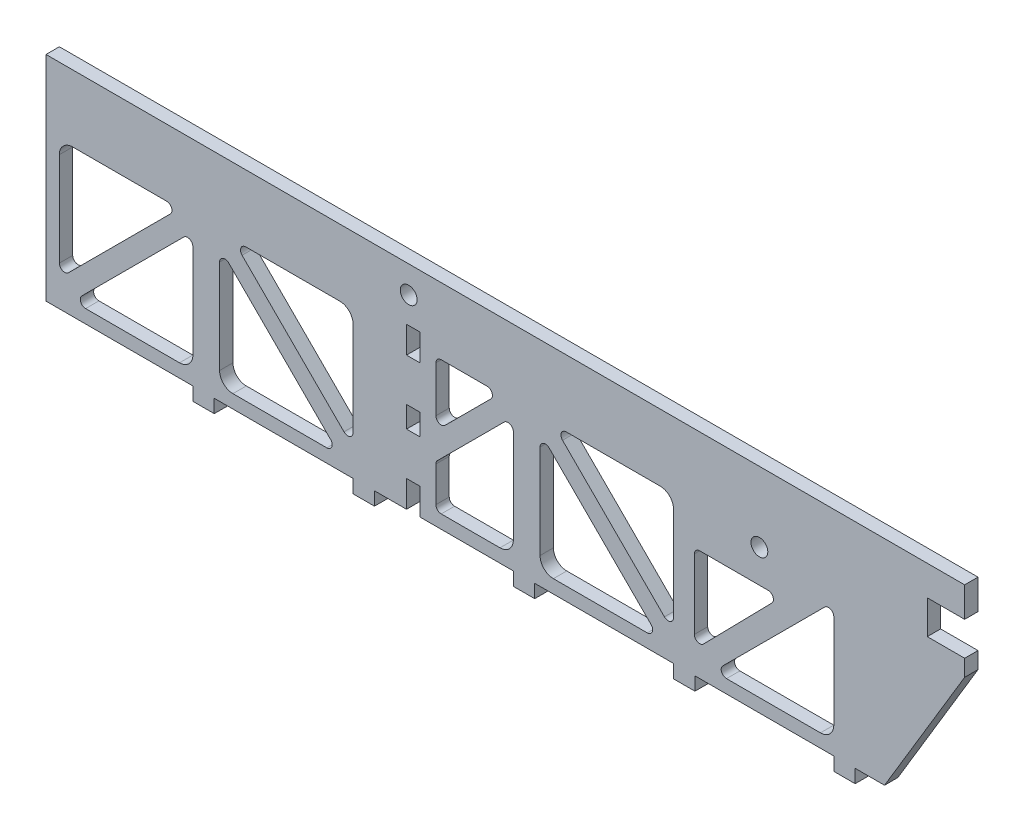
SolidWorks part; units mm, degrees
material "Pine"
ref_plane "Front Plane" through (0, 0, 0) normal (0, 0, 1) x (1, 0, 0)
ref_plane "Top Plane" through (0, 0, 0) normal (0, 1, 0) x (1, 0, 0)
ref_plane "Right Plane" through (0, 0, 0) normal (1, 0, 0) x (0, 0, -1)
sketch "Model" plane through (0, 0, 0) normal (0, 0, 1) x (1, 0, 0)
  line L0 (312.6855, 15.1239) -> (345.2281, 48.2988)
  line L1 (343.4149, 52.6175) -> (310.8722, 52.6175)
  line L2 (308.3322, 50.0775) -> (308.3322, 16.9026)
  line L8 (171.2321, 6.35) -> (215.9, 6.35)
  line L9 (217.9139, 59.1639) -> (169.4361, 10.6861)
  line L10 (222.25, 57.3679) -> (222.25, 12.7)
  line L11 (234.95, 57.3679) -> (234.95, 12.7)
  line L12 (239.2861, 59.1639) -> (287.7639, 10.6861)
  line L13 (241.3, 6.35) -> (285.9679, 6.35)
  line L14 (294.1139, 17.0361) -> (245.6361, 65.5139)
  line L15 (247.4321, 69.85) -> (292.1, 69.85)
  line L16 (298.45, 63.5) -> (298.45, 18.8321)
  line L17 (323.6321, 6.35) -> (368.3, 6.35)
  line L18 (370.3139, 59.1639) -> (321.8361, 10.6861)
  line L19 (374.65, 57.3679) -> (374.65, 12.7)
  line L20 (18.8321, 6.35) -> (63.5, 6.35)
  line L21 (17.0361, 10.6861) -> (65.5139, 59.1639)
  line L22 (69.85, 57.3679) -> (69.85, 12.7)
  line L23 (82.55, 57.3679) -> (82.55, 12.7)
  line L24 (86.8861, 59.1639) -> (135.3639, 10.6861)
  line L25 (88.9, 6.35) -> (133.5679, 6.35)
  line L26 (93.2361, 65.5139) -> (141.7139, 17.0361)
  line L27 (95.0321, 69.85) -> (139.7, 69.85)
  line L28 (146.05, 63.5) -> (146.05, 18.8321)
  line L29 (163.0861, 17.0361) -> (211.5639, 65.5139)
  line L30 (158.75, 63.5) -> (158.75, 18.8321)
  line L31 (165.1, 69.85) -> (209.7679, 69.85)
  line L35 (419.1, 87.376) -> (419.1, 71.374)
  line L36 (436.88, 87.376) -> (419.1, 87.376)
  line L37 (436.88, 87.376) -> (436.88, 95.25)
  line L38 (0, 95.25) -> (436.88, 95.25)
  line L39 (0, 0) -> (0, 95.25)
  line L40 (0, 0) -> (398.78, 0)
  line L41 (436.88, 63.5) -> (398.78, 0)
  line L42 (436.88, 63.5) -> (436.88, 71.374)
  line L43 (419.1, 71.374) -> (436.88, 71.374)
  line L44 (6.35, 63.5) -> (6.35, 18.8321)
  line L45 (12.7, 69.85) -> (57.3679, 69.85)
  line L46 (59.1639, 65.5139) -> (10.6861, 17.0361)
  arc A0 (215.9, 6.35) -> (222.25, 12.7) centre (215.9, 12.7) ccw
  arc A1 (169.4361, 10.6861) -> (171.2321, 6.35) centre (171.2321, 8.89) ccw
  arc A2 (222.25, 57.3679) -> (217.9139, 59.1639) centre (219.71, 57.3679) ccw
  arc A3 (239.2861, 59.1639) -> (234.95, 57.3679) centre (237.49, 57.3679) ccw
  arc A4 (285.9679, 6.35) -> (287.7639, 10.6861) centre (285.9679, 8.89) ccw
  arc A5 (234.95, 12.7) -> (241.3, 6.35) centre (241.3, 12.7) ccw
  arc A6 (247.4321, 69.85) -> (245.6361, 65.5139) centre (247.4321, 67.31) ccw
  arc A7 (298.45, 63.5) -> (292.1, 69.85) centre (292.1, 63.5) ccw
  arc A8 (294.1139, 17.0361) -> (298.45, 18.8321) centre (295.91, 18.8321) ccw
  arc A9 (321.8361, 10.6861) -> (323.6321, 6.35) centre (323.6321, 8.89) ccw
  arc A10 (374.65, 57.3679) -> (370.3139, 59.1639) centre (372.11, 57.3679) ccw
  arc A11 (368.3, 6.35) -> (374.65, 12.7) centre (368.3, 12.7) ccw
  arc A12 (63.5, 6.35) -> (69.85, 12.7) centre (63.5, 12.7) ccw
  arc A13 (17.0361, 10.6861) -> (18.8321, 6.35) centre (18.8321, 8.89) ccw
  arc A14 (69.85, 57.3679) -> (65.5139, 59.1639) centre (67.31, 57.3679) ccw
  arc A15 (86.8861, 59.1639) -> (82.55, 57.3679) centre (85.09, 57.3679) ccw
  arc A16 (133.5679, 6.35) -> (135.3639, 10.6861) centre (133.5679, 8.89) ccw
  arc A17 (82.55, 12.7) -> (88.9, 6.35) centre (88.9, 12.7) ccw
  arc A18 (95.0321, 69.85) -> (93.2361, 65.5139) centre (95.0321, 67.31) ccw
  arc A19 (146.05, 63.5) -> (139.7, 69.85) centre (139.7, 63.5) ccw
  arc A20 (141.7139, 17.0361) -> (146.05, 18.8321) centre (143.51, 18.8321) ccw
  arc A21 (158.75, 18.8321) -> (163.0861, 17.0361) centre (161.29, 18.8321) ccw
  arc A22 (165.1, 69.85) -> (158.75, 63.5) centre (165.1, 63.5) ccw
  arc A23 (211.5639, 65.5139) -> (209.7679, 69.85) centre (209.7679, 67.31) ccw
  arc A24 (345.2281, 48.2988) -> (343.4149, 52.6175) centre (343.4149, 50.0775) ccw
  arc A25 (310.8722, 52.6175) -> (308.3322, 50.0775) centre (310.8722, 50.0775) ccw
  arc A26 (312.6855, 15.1239) -> (308.3322, 16.9026) centre (310.8722, 16.9026) cw
  arc A27 (6.35, 18.8321) -> (10.6861, 17.0361) centre (8.89, 18.8321) ccw
  arc A28 (12.7, 69.85) -> (6.35, 63.5) centre (12.7, 63.5) ccw
  arc A29 (59.1639, 65.5139) -> (57.3679, 69.85) centre (57.3679, 67.31) ccw
  circle A30 centre (172.4917, 88.8013) radius 4
  circle A31 centre (339.2605, 68.3246) radius 4
  circle A32 centre (172.4917, 88.8013) radius 168.021 construction
  dimension "D2" = 6.4487
  dimension "D3" = 172.4917
  dimension "D4" = 8
  dimension "D5" = 20.4767
  dimension "D6" = 8
  dimension "D8" = 2.54
  dimension "D1" = 95.25
  dimension "D7" = 166.7688
extrude "Boss-Extrude2" add sketch "Model" along normal blind 6.35
sketch "Sketch1" plane through (0, 0, 6.35) normal (0, 0, 1) x (1, 0, 0)
  line L0 (69.85, 12.7) -> (69.85, 0) construction
  line L1 (146.05, 95.25) -> (146.05, 0) construction
  line L2 (146.05, 18.8321) -> (146.05, 63.5) construction
  line L3 (0, 0) -> (398.78, 0) construction
  line L4 (222.25, 95.25) -> (222.25, 0) construction
  line L5 (222.25, 12.7) -> (222.25, 57.3679) construction
  line L6 (298.45, 18.8321) -> (298.45, 0) construction
  line L7 (146.05, 0) -> (156.21, 0)
  line L8 (69.85, 0) -> (80.01, 0)
  line L9 (69.85, 0) -> (69.85, -6.35)
  line L10 (69.85, -6.35) -> (80.01, -6.35)
  line L11 (80.01, 0) -> (80.01, -6.35)
  line L16 (222.25, 0) -> (232.41, 0)
  line L17 (222.25, 0) -> (222.25, -6.35)
  line L18 (222.25, -6.35) -> (232.41, -6.35)
  line L19 (232.41, 0) -> (232.41, -6.35)
  line L20 (146.05, 0) -> (146.05, -6.35)
  line L21 (146.05, -6.35) -> (156.21, -6.35)
  line L22 (156.21, 0) -> (156.21, -6.35)
  line L24 (374.65, 12.7) -> (374.65, 0) construction
  line L25 (374.65, 12.7) -> (374.65, 57.3679) construction
  line L27 (298.45, 0) -> (308.61, 0)
  line L28 (298.45, 0) -> (298.45, -6.35)
  line L29 (298.45, -6.35) -> (308.61, -6.35)
  line L30 (308.61, 0) -> (308.61, -6.35)
  line L31 (374.65, 0) -> (384.81, 0)
  line L32 (374.65, 0) -> (374.65, -6.35)
  line L33 (374.65, -6.35) -> (384.81, -6.35)
  line L34 (384.81, 0) -> (384.81, -6.35)
  line L39 (0, 101.6) -> (436.88, 101.6)
  line L53 (0, 95.25) -> (0, 101.6)
  line L55 (436.88, 95.25) -> (436.88, 101.6)
  line L56 (436.88, 95.25) -> (0, 95.25) construction
  line L57 (0, 95.25) -> (436.88, 95.25)
  arc A0 (368.3, 6.35) -> (374.65, 12.7) centre (368.3, 12.7) ccw construction
  dimension "D1" = 10.16
  dimension "D2" = 6.35
  dimension "D3" = 10.16
  dimension "D4" = 6.35
  dimension "D5" = 10.16
  dimension "D6" = 10.16
  dimension "D7" = 10.16
  dimension "D13" = 6.35
extrude "Boss-Extrude3" add sketch "Sketch1" against normal up to surface (6.35 mm away) up to face at (321.5295, 39.2174, 0)
sketch "Sketch2" plane through (0, 0, 6.35) normal (0, 0, 1) x (1, 0, 0)
  line L0 (156.21, 0) -> (222.25, 0) construction
  line L1 (165.1, 79.7539) -> (185.42, 79.7539)
  line L2 (165.1, 79.7539) -> (165.1, 0)
  line L3 (165.1, 0) -> (185.42, 0)
  line L4 (185.42, 79.7539) -> (185.42, 0)
  line L5 (158.75, 63.5) -> (158.75, 18.8321) construction
  line L7 (171.45, 0) -> (177.8, 0)
  line L8 (171.45, 0) -> (171.45, 12.7)
  line L9 (171.45, 12.7) -> (177.8, 12.7)
  line L10 (177.8, 0) -> (177.8, 12.7)
  line L11 (171.45, 33.02) -> (177.8, 33.02)
  line L12 (171.45, 33.02) -> (171.45, 43.18)
  line L13 (171.45, 43.18) -> (177.8, 43.18)
  line L14 (177.8, 33.02) -> (177.8, 43.18)
  line L15 (171.45, 63.5) -> (177.8, 63.5)
  line L16 (171.45, 63.5) -> (171.45, 76.2)
  line L17 (171.45, 76.2) -> (177.8, 76.2)
  line L18 (177.8, 63.5) -> (177.8, 76.2)
  line L19 (146.05, -6.35) -> (156.21, -6.35) construction
  dimension "D1" = 6.35
  dimension "D2" = 20.32
  dimension "D3" = 6.35
  dimension "D4" = 6.35
  dimension "D5" = 6.35
  dimension "D6" = 12.7
  dimension "D7" = 20.32
  dimension "D8" = 20.32
  dimension "D9" = 10.16
  dimension "D10" = 12.7
extrude "Boss-Extrude4" add sketch "Sketch2" against normal up to surface (6.35 mm away) contours L10 L3 L4 L1 L2 L8 L9 L18 L15 L16 L17 L14 L11 L12 L13 region at (175.26, 78.9309, 6.35) up to face at (321.5295, 39.2174, 0)
extrude "Cut-Extrude1" cut sketch "Sketch2<3>" along direction (0, 0, 1) on the side against the normal up to surface (6.35 mm away) from surface contours L3 L10 L9 L8 | L15 L18 L17 L16 region at (174.625, 6.35, 6.35) region at (174.625, 69.85, 6.35) up to face at (174.625, 9.525, 0) starting at face at (174.625, 9.525, 6.35)
sketch "Sketch2<3>" plane through (0, 0, 6.35) normal (0, 0, 1) x (1, 0, 0) same geometry as "Sketch2"
sketch "Sketch3" plane through (0, 0, 6.35) normal (0, 0, 1) x (1, 0, 0)
  line L1 (154.8502, 72.8404) -> (168.7325, 72.8404)
  line L2 (154.8502, 72.8404) -> (154.8502, 13.7288)
  line L3 (154.8502, 13.7288) -> (168.7325, 13.7288)
  line L4 (168.7325, 72.8404) -> (168.7325, 13.7288)
extrude "Boss-Extrude5" add sketch "Sketch3" against normal up to surface (6.35 mm away) up to face at (174.625, 69.85, 0)
sketch "Sketch4" plane through (0, 0, 6.35) normal (0, 0, 1) x (1, 0, 0)
  line L0 (209.7679, 69.85) -> (185.42, 69.85) construction
  line L1 (185.42, 39.37) -> (211.5639, 65.5139) construction
  line L2 (185.42, 69.85) -> (185.42, 39.37) construction
  line L3 (185.42, 6.35) -> (215.9, 6.35) construction
  line L4 (185.42, 26.67) -> (185.42, 6.35) construction
  line L5 (209.7679, 69.85) -> (187.96, 69.85)
  line L6 (189.7561, 43.7061) -> (211.5639, 65.5139)
  line L7 (185.42, 67.31) -> (185.42, 45.5021)
  line L8 (187.96, 6.35) -> (215.9, 6.35)
  line L9 (185.42, 25.6179) -> (185.42, 8.89)
  line L10 (185.42, 45.5021) -> (185.42, 39.37)
  line L11 (185.42, 39.37) -> (189.7561, 43.7061)
  line L12 (185.42, 67.31) -> (185.42, 69.85)
  line L13 (185.42, 69.85) -> (187.96, 69.85)
  line L14 (185.42, 8.89) -> (185.42, 6.35)
  line L15 (185.42, 6.35) -> (187.96, 6.35)
  line L16 (185.42, 8.89) -> (185.42, 6.35)
  line L17 (217.9139, 59.1639) -> (185.42, 26.67) construction
  line L18 (217.9139, 59.1639) -> (186.1639, 27.4139)
  line L19 (185.42, 25.6179) -> (185.42, 26.67)
  line L20 (185.42, 26.67) -> (186.1639, 27.4139)
  arc A0 (187.96, 69.85) -> (185.42, 67.31) centre (187.96, 67.31) ccw
  arc A1 (189.7561, 43.7061) -> (185.42, 45.5021) centre (187.96, 45.5021) cw
  arc A2 (187.96, 6.35) -> (185.42, 8.89) centre (187.96, 8.89) cw
  arc A3 (185.42, 25.6179) -> (186.1639, 27.4139) centre (187.96, 25.6179) cw
  dimension "D1" = 2.54
  dimension "D2" = 2.54
extrude "Boss-Extrude6" add sketch "Sketch4" against normal up to surface (6.35 mm away) contours L11 A1 L10 | A0 L13 L12 | L15 A2 L14 | L19 A3 L20 region at (186.5486, 42.0946, 6.35) region at (185.9874, 69.2826, 6.35) region at (185.9874, 6.9174, 6.35) region at (185.5728, 26.6067, 6.35) up to face at (174.625, 69.85, 0)
